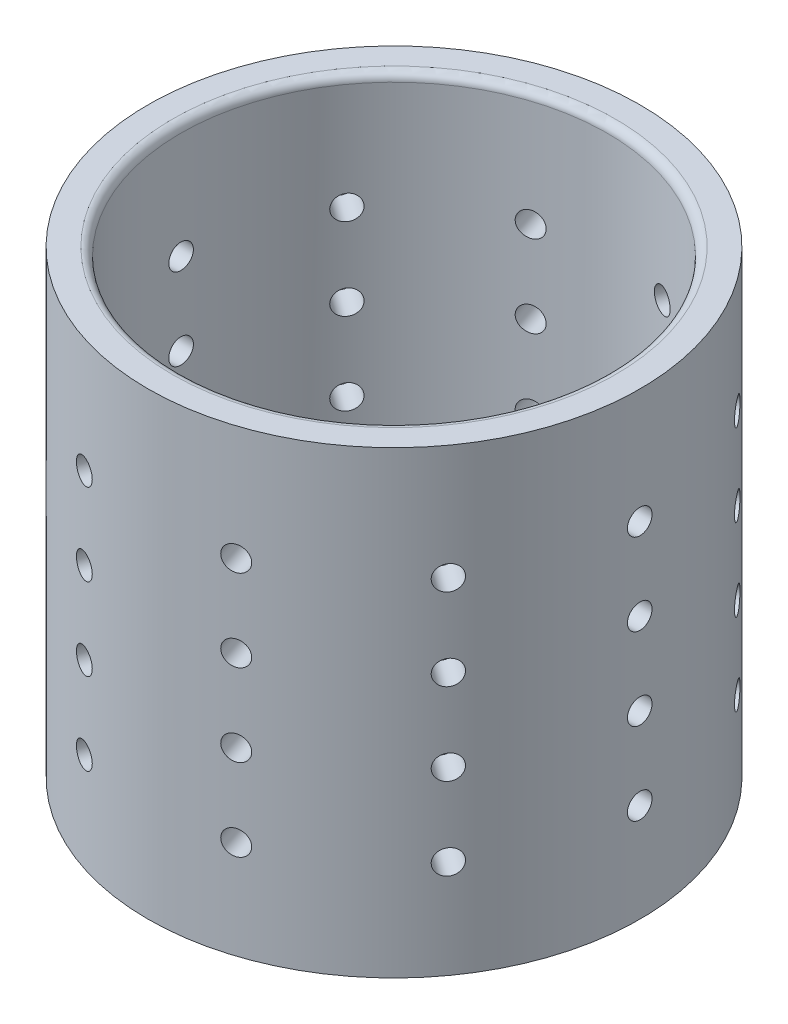
SolidWorks part; units mm, degrees
ref_plane "Front Plane" through (0, 0, 0) normal (0, 0, 1) x (1, 0, 0)
ref_plane "Top Plane" through (0, 0, 0) normal (0, 1, 0) x (1, 0, 0)
ref_plane "Right Plane" through (0, 0, 0) normal (1, 0, 0) x (0, 0, -1)
sketch "Sketch1" plane through (0, 0, 0) normal (0, 1, 0) x (1, 0, 0)
  circle A0 centre (0, 0) radius 15
  dimension "D1" = 30
extrude "Boss-Extrude1" add sketch "Sketch1" along normal blind 3
sketch "Sketch2" plane through (0, 3, 0) normal (0, 1, 0) x (1, 0, 0)
  circle A0 centre (0, 0) radius 5
  dimension "D1" = 10
extrude "Boss-Extrude2" add sketch "Sketch2" along normal blind 10
sketch "Sketch3" plane through (0, 3, 0) normal (0, 1, 0) x (1, 0, 0)
  circle A0 centre (0, 0) radius 15
  circle A1 centre (0, 0) radius 13
  dimension "D1" = 2
extrude "Boss-Extrude3" add sketch "Sketch3" along normal blind 25
sketch "Sketch4" plane through (0, 13, 0) normal (0, 1, 0) x (1, 0, 0)
  line L0 (-5, 0) -> (5, 0) construction
  line L2 (-1.85, -1.5) -> (1.85, -1.5)
  line L3 (-1.85, -1.5) -> (-1.85, 1.5)
  line L4 (-1.85, 1.5) -> (1.85, 1.5)
  line L5 (1.85, -1.5) -> (1.85, 1.5)
  line L6 (-1.85, -1.5) -> (1.85, 1.5) construction
  line L7 (-1.85, 1.5) -> (1.85, -1.5) construction
  circle A0 centre (0, 0) radius 5 construction
  circle A1 centre (0, 0) radius 5 construction
  point P7 (0, 0)
  dimension "D1" = 3.7
  dimension "D2" = 3
extrude "Cut-Extrude1" cut sketch "Sketch4" against normal blind 7
sketch "Sketch5" plane through (0, 6, 0) normal (0, 1, 0) x (1, 0, 0)
  circle A0 centre (0, 0) radius 1.25
  dimension "D1" = 2.5
extrude "Cut-Extrude2" cut sketch "Sketch5" against normal through all
fillet "Fillet1" radius 1 5 edges at (0, 13, 5) (0, 13, -1.5) (-1.85, 13, 0) (0, 13, 1.5) (1.85, 13, 0)
fillet "Fillet2" radius 0.5 1 edges at (0, 28, 13)
fillet "Fillet3" radius 3 2 edges at (0, 3, 13) (0, 3, 5)
ref_plane "Plane1" through (-15, 0, 0) normal (-1, 0, 0) x (0, 0, 1)
sketch "Sketch6" plane through (-15, 0, 0) normal (-1, 0, 0) x (0, 0, 1)
  line L0 (0, 28) -> (0, 0) construction
  line L1 (15, 28) -> (-15, 28) construction
  circle A0 centre (0, 21) radius 0.75
  circle A1 centre (0, 16) radius 0.75
  circle A2 centre (0, 11) radius 0.75
  circle A3 centre (0, 6) radius 0.75
  dimension "D1" = 1.5
  dimension "D6" = 1.5
  dimension "D7" = 1.5
  dimension "D8" = 1.5
  dimension "D2" = 7
  dimension "D3" = 5
  dimension "D4" = 5
  dimension "D5" = 5
extrude "Cut-Extrude3" cut sketch "Sketch6" against normal blind 3
ref_axis "Axis1" through (0, 27.5, 0) along (0, -1, 0)
pattern_circular "CirPattern1" count 10 over 360 about axis through (0, 27.5, 0) along (0, -1, 0) of "Cut-Extrude3"
sketch "Sketch7" plane through (-15, 0, 0) normal (-1, 0, 0) x (0, 0, 1)
  line L0 (-15, 0) -> (15, 0) construction
  circle A0 centre (0, 0) radius 1.5
  dimension "D1" = 3
extrude "Cut-Extrude4" cut sketch "Sketch7" against normal blind 15
fillet "Fillet4" radius 1 1 edges at (-1.2356, 1.488, -0.1895)
